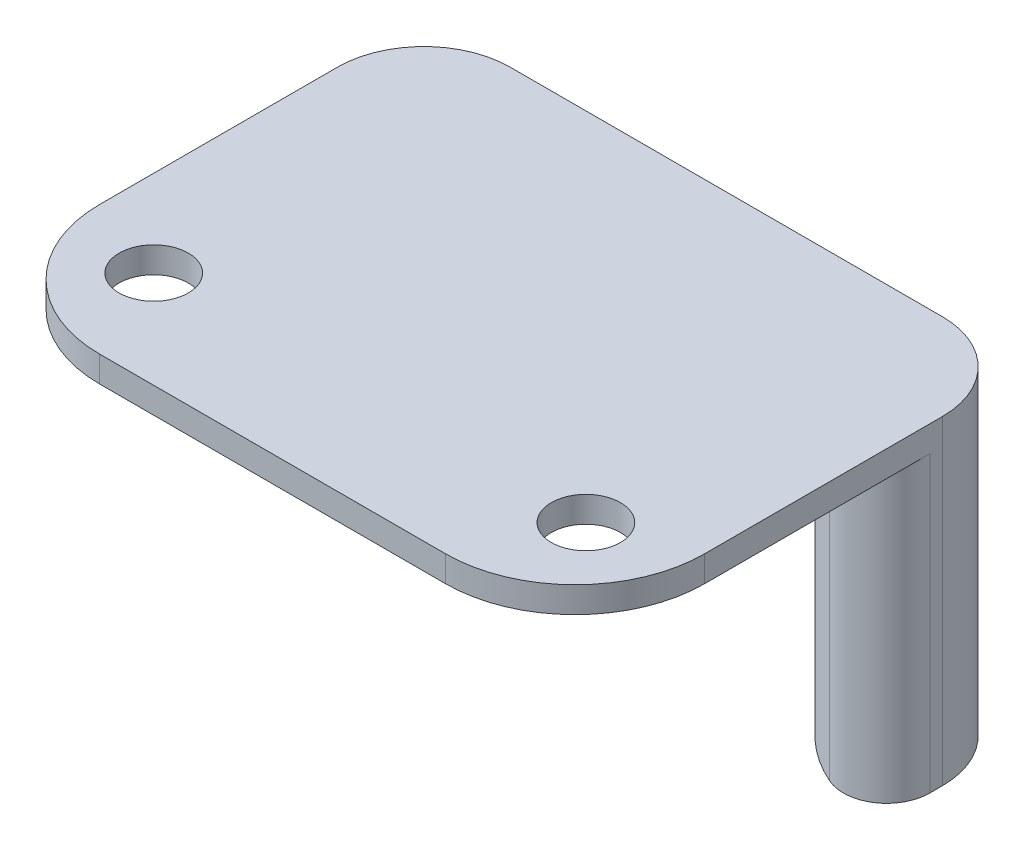
SolidWorks part; units mm, degrees
ref_plane "Płaszczyzna przednia" through (0, 0, 0) normal (0, 0, 1) x (1, 0, 0)
ref_plane "Płaszczyzna górna" through (0, 0, 0) normal (0, 1, 0) x (1, 0, 0)
ref_plane "Płaszczyzna prawa" through (0, 0, 0) normal (1, 0, 0) x (0, 0, -1)
sketch "Szkic1" plane through (0, 0, 0) normal (0, 1, 0) x (1, 0, 0)
  line L0 (-10, 0) -> (10, 0) construction
  line L1 (0, 0) -> (0, 6) construction
  line L7 (-14, -4.5) -> (14, -4.5)
  line L8 (-14, -4.5) -> (-14, 16.5)
  line L9 (-14, 16.5) -> (14, 16.5)
  line L10 (14, -4.5) -> (14, 16.5)
  line L11 (-14, -4.5) -> (14, 16.5) construction
  line L12 (-14, 16.5) -> (14, -4.5) construction
  circle A0 centre (10, 0) radius 1.6
  circle A1 centre (-10, 0) radius 1.6
  point P4 (0, 0)
  point P7 (0, 0)
  dimension "D1" = 3.2
  dimension "D2" = 3.2
  dimension "D3" = 28
  dimension "D4" = 21
  dimension "D5" = 20
  dimension "D6" = 6
extrude "Dodanie-wyciągnięcie1" add sketch "Szkic1" along normal blind 1.2
sketch "Szkic2" plane through (0, 0, 0) normal (0, -1, 0) x (1, 0, 0)
  line L14 (14, -16.5) -> (-14, -16.5) construction
  line L15 (-14, -16.5) -> (-14, 4.5) construction
  line L16 (-14, -16.5) -> (-14, -9.5)
  line L17 (-14, -16.5) -> (-7, -16.5)
  line L18 (0, -55) -> (0, 55) construction
  line L19 (14, -16.5) -> (7, -16.5)
  line L20 (14, -16.5) -> (14, -9.5)
  arc A4 (-7, -16.5) -> (-14, -9.5) centre (-14, -16.5) ccw
  arc A5 (7, -16.5) -> (14, -9.5) centre (14, -16.5) cw
  dimension "D1" = 7
extrude "Dodanie-wyciągnięcie2" add sketch "Szkic2" along normal blind 13.6
fillet "Zaokrąglenie3" radius 6 2 edges at (14, 0.6, 4.5) (-14, 0.6, 4.5)
fillet "Zaokrąglenie1" radius 4 2 edges at (14, -6.2, -16.5) (-14, -6.2, -16.5)
fillet "Zaokrąglenie2" radius 2 4 edges at (-14, -6.8, -9.5) (-7, -6.8, -16.5) (14, -6.8, -9.5) (7, -6.8, -16.5)
